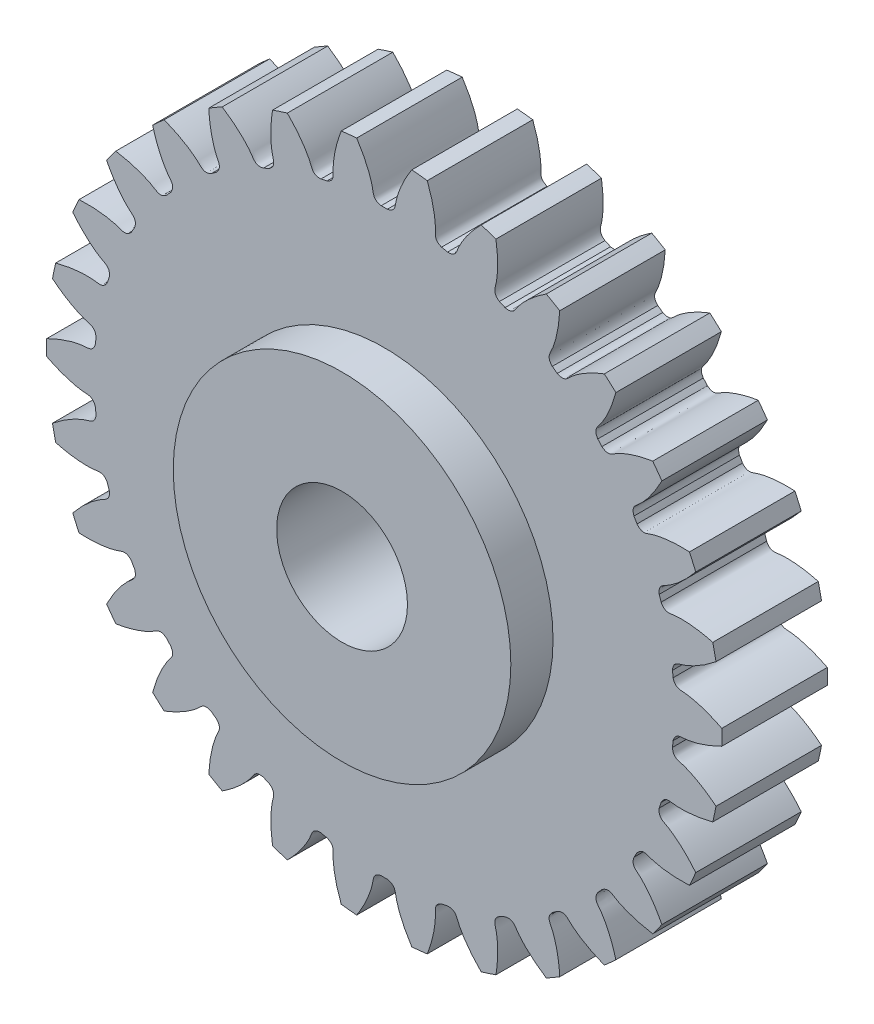
SolidWorks part; units mm, degrees
ref_plane "前视基准面" through (0, 0, 0) normal (0, 0, 1) x (1, 0, 0)
ref_plane "上视基准面" through (0, 0, 0) normal (0, 1, 0) x (1, 0, 0)
ref_plane "右视基准面" through (0, 0, 0) normal (1, 0, 0) x (0, 0, -1)
sketch "草图1" plane through (0, 0, 0) normal (0, 0, 1) x (1, 0, 0)
  circle A0 centre (0, 0) radius 8
extrude "凸台-拉伸1" add sketch "草图1" along normal blind 2.5
ref_axis "基准轴1" through (0, 0, -0.15) along (0, 0, 1)
sketch "草图2" plane through (0, 0, 0) normal (0, 0, 1) x (1, 0, 0)
  line L0 (0, 0) -> (0, 8) construction
  circle A0 centre (0, 0) radius 8 construction
  arc A1 (0.0728, 6.8746) -> (-0.0728, 6.8746) centre (0, 0) ccw
  arc A2 (1.6832, 9.0953) -> (-1.6832, 9.0953) centre (0, 0) ccw
  spline S0 degree 3 poles (0.0728, 6.8746) (0.2541, 6.9065) (0.2552, 7.0236) (0.2795, 7.1443) (0.285, 7.1691) (0.2916, 7.1965) (0.2995, 7.2264) (0.3088, 7.259) (0.3196, 7.294) (0.3319, 7.3315) (0.3459, 7.3714) (0.3617, 7.4137) (0.3794, 7.4582) (0.3991, 7.505) (0.4208, 7.554) (0.4447, 7.605) (0.4709, 7.6581) (0.4994, 7.7132) (0.5303, 7.7702) (0.5638, 7.829) (0.5999, 7.8895) (0.6387, 7.9517) (0.6803, 8.0155) (0.7247, 8.0807) (0.772, 8.1474) (0.8224, 8.2154) (0.8758, 8.2845) (0.9324, 8.3548) (0.9921, 8.4261) (1.0552, 8.4983) (1.1215, 8.5713) (1.1913, 8.6451) (1.2645, 8.7194) (1.3411, 8.7942) (1.4213, 8.8694) (1.5345, 8.9713) (1.6227, 9.046) (1.6832, 9.0953) knots 0 0 0 0 0.115324 0.123413 0.132512 0.142623 0.153745 0.165878 0.179022 0.193177 0.208343 0.22452 0.241708 0.259907 0.279117 0.299338 0.320571 0.342814 0.366068 0.390334 0.41561 0.441898 0.469196 0.497506 0.526827 0.557158 0.588501 0.620855 0.65422 0.688595 0.723982 0.76038 0.797789 0.836209 0.87564 0.916083 1 1 1 1
  spline S1 degree 3 poles (-0.0728, 6.8746) (-0.2541, 6.9065) (-0.2552, 7.0236) (-0.2795, 7.1443) (-0.285, 7.1691) (-0.2916, 7.1965) (-0.2995, 7.2264) (-0.3088, 7.259) (-0.3196, 7.294) (-0.3319, 7.3315) (-0.3459, 7.3714) (-0.3617, 7.4137) (-0.3794, 7.4582) (-0.3991, 7.505) (-0.4208, 7.554) (-0.4447, 7.605) (-0.4709, 7.6581) (-0.4994, 7.7132) (-0.5303, 7.7702) (-0.5638, 7.829) (-0.5999, 7.8895) (-0.6387, 7.9517) (-0.6803, 8.0155) (-0.7247, 8.0807) (-0.772, 8.1474) (-0.8224, 8.2154) (-0.8758, 8.2845) (-0.9324, 8.3548) (-0.9921, 8.4261) (-1.0552, 8.4983) (-1.1215, 8.5713) (-1.1913, 8.6451) (-1.2645, 8.7194) (-1.3411, 8.7942) (-1.4213, 8.8694) (-1.5345, 8.9713) (-1.6227, 9.046) (-1.6832, 9.0953) knots 0 0 0 0 0.115324 0.123413 0.132512 0.142623 0.153745 0.165878 0.179022 0.193177 0.208343 0.22452 0.241708 0.259907 0.279117 0.299338 0.320571 0.342814 0.366068 0.390334 0.41561 0.441898 0.469196 0.497506 0.526827 0.557158 0.588501 0.620855 0.65422 0.688595 0.723982 0.76038 0.797789 0.836209 0.87564 0.916083 1 1 1 1
extrude "切除-拉伸1" cut sketch "草图2" along normal through all
pattern_circular "阵列(圆周)1" count 30 every 12 about axis through (0, 0, -0.15) along (0, 0, 1) of "切除-拉伸1"
sketch "草图3" plane through (0, 0, 0) normal (0, 0, 1) x (1, 0, 0)
  circle A0 centre (0, 0) radius 7.5 construction
  dimension "Dn" = 15
sketch "草图5" plane through (0, 0, 0) normal (0, 0, -1) x (-1, 0, 0)
  circle A0 centre (0, 0) radius 4
  dimension "D1" = 8
extrude "凸台-拉伸2" add sketch "草图5" along normal blind 1
sketch "草图6" plane through (0, 0, 2.5) normal (0, 0, 1) x (1, 0, 0)
  circle A0 centre (0, 0) radius 4
  dimension "D1" = 8
extrude "凸台-拉伸3" add sketch "草图6" along normal blind 1
sketch "草图4" plane through (0, 0, 0) normal (0, 0, -1) x (-1, 0, 0)
  line L0 (0, 0) -> (0, 0.5383) construction
  arc A0 (-0.775, 1.3423) -> (0.775, 1.3423) centre (0, 0) ccw
  arc A1 (-0.775, 1.3423) -> (0.775, 1.3423) centre (0, 0) cw
  dimension "D1" = 3.1
extrude "切除-拉伸2" cut sketch "草图4" along normal up to next from surface starting at face at (4, 0, 3.5)
